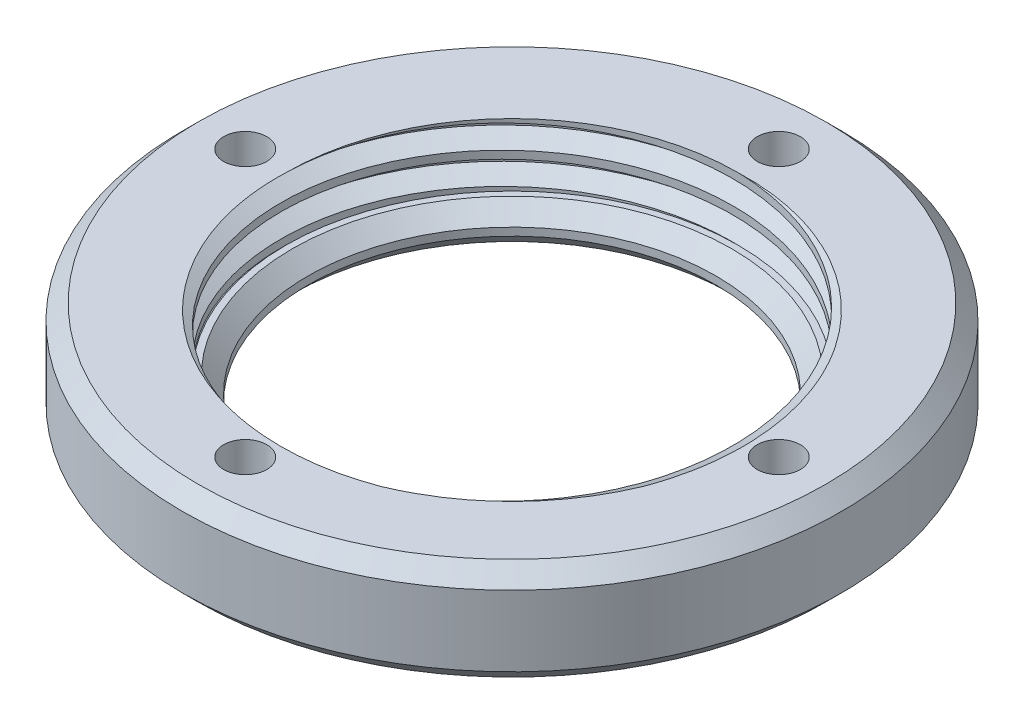
SolidWorks part; units mm, degrees
ref_plane "Спереди" through (0, 0, 0) normal (0, 0, 1) x (1, 0, 0)
ref_plane "Сверху" through (0, 0, 0) normal (0, 1, 0) x (1, 0, 0)
ref_plane "Справа" through (0, 0, 0) normal (1, 0, 0) x (0, 0, -1)
sketch "Эскиз1" plane through (0, 0, 0) normal (0, 1, 0) x (1, 0, 0)
  circle A0 centre (0, 0) radius 13
  circle A1 centre (0, 0) radius 21
  dimension "D1" = 26
  dimension "D2" = 42
extrude "Бобышка-Вытянуть1" add sketch "Эскиз1" along normal blind 6.5
sketch "Эскиз2" plane through (0, 6.5, 0) normal (0, 1, 0) x (1, 0, 0)
  circle A0 centre (0, 0) radius 14.4
  dimension "D1" = 28.8
extrude "Вырез-Вытянуть1" cut sketch "Эскиз2" against normal blind 4
thread "Резьба1" pitch 2 method cut profile "Профиль резьбы1" start angle 0, offset 2, length 0, pitch 2, diameter 28.8
ref_plane "Плоскость1" through (-14.4, 8.5, 0) normal (0, 0, 1) x (-1, 0, 0)
sketch "Профиль резьбы1" plane through (-14.4, 8.5, 0) normal (0, 0, 1) x (-1, 0, 0)
  line L0 (0, 0) -> (0, 2) construction
  line L1 (0, 0) -> (1.0825, 0.625)
  line L2 (1.0825, 0.625) -> (1.0825, 0.875)
  line L3 (1.0825, 0.875) -> (0, 1.5)
  line L4 (1.0825, 0.75) -> (0, 0.75) construction
  line L11 (0, 0) -> (0, 1.5)
  point P2 (0, 0)
  dimension "Pitch" = 2
  dimension "Profile_Angle" = 60
  dimension "Profile_Land" = 0.25
  dimension "Profile_Height" = 1.0825
sketch "Эскиз5" plane through (0, 0, 0) normal (0, -1, 0) x (1, 0, 0)
  circle A0 centre (0, 0) radius 17 construction
  circle A1 centre (0, 17) radius 1.375
  circle A2 centre (17, 0) radius 1.375
  circle A3 centre (0, -17) radius 1.375
  circle A4 centre (-17, 0) radius 1.375
  point P5 (0, 0)
  point P6 (0, 0)
  dimension "D1" = 34
  dimension "D2" = 2.75
  dimension "D3" = 4
extrude "Вырез-Вытянуть2" cut sketch "Эскиз5" against normal through all
chamfer "Фаска1" distance 1 angle 45 4 edges at (0, 2.5, 13) (0, 0, 13) (0, 6.5, 21) (0, 0, 21)
equation "\"print_offset\"= 0.5"
equation "\"radial_bearing_d1\"= 7.7"
equation "\"radial_bearing_d2\"= 16"
equation "\"radial_bearing_h\"= 5"
equation "\"shaft_d\"= 6"
equation "\"shaft_h\" = 60"
equation "\"central_hole_d\"= 20"
equation "\"sitting_screws_d\"= 34"
equation "\"screw_d\"= 2"
equation "\"screw_hh_d\"= 3.4"
equation "\"screw_h\"= 8"
equation "\"screw_hh_h\"= 2"
equation "\"motor_screw_d\"= 3"
equation "\"motor_screw_hh_d\"= 5.6"
equation "\"motor_screw_h\" = 20"
equation "\"motor_screw_hh_h\"= 2"
equation "\"motor_nut_d\"= 5.4"
equation "\"motor_nut_h\"= 2.8"
equation "\"D2@Эскиз1\"=\"sitting_screws_d\"+8"
equation "\"D1@Эскиз1\"=\"sitting_screws_d\"-8"
equation "\"D1@Эскиз5\"=\"sitting_screws_d\""
equation "\"D2@Эскиз5\"=3-\"print_offset\"/2"
